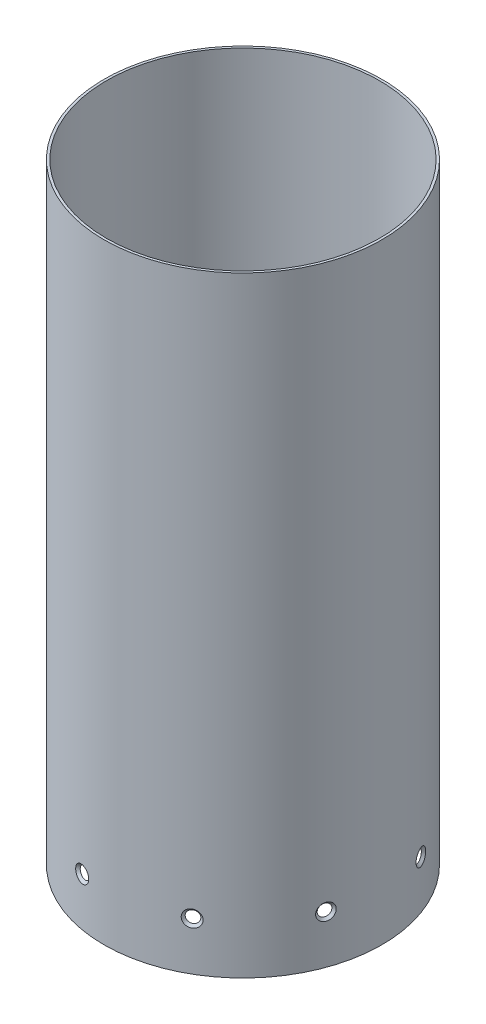
SolidWorks part; units mm, degrees
material "E-Glass Fiber"
ref_plane "Front Plane" through (0, 0, 0) normal (0, 0, 1) x (1, 0, 0)
ref_plane "Top Plane" through (0, 0, 0) normal (0, 1, 0) x (1, 0, 0)
ref_plane "Right Plane" through (0, 0, 0) normal (1, 0, 0) x (0, 0, -1)
sketch "Sketch1" plane through (0, 0, 0) normal (0, 1, 0) x (1, 0, 0)
  circle A0 centre (0, 0) radius 86.5
  circle A1 centre (0, 0) radius 85
extrude "Boss-Extrude1" add sketch "Sketch1" along normal blind 380
ref_plane "Plane2" through (0, 30, 0) normal (0, -1, 0) x (-1, 0, 0)
ref_plane "Plane1" through (-86.5, 0, 0) normal (-1, 0, 0) x (0, 0, 1)
sketch "Sketch2" plane through (-86.5, 0, 0) normal (-1, 0, 0) x (0, 0, 1)
  line L0 (-86.5, 0) -> (86.5, 0) construction
  circle A0 centre (0, 30) radius 2.75
  dimension "D1" = 30
extrude "Cut-Extrude1" cut sketch "Sketch2" against normal up to next
sketch "Sketch4" plane through (0, 30, 0) normal (0, -1, 0) x (1, 0, 0)
  line L1 (-93.9937, 0) -> (-74.5658, 0) construction
  line L6 (-86.3554, 0) -> (-86.3554, -5) construction
  line L7 (-86.3554, -5) -> (-81.3554, 0)
  line L8 (-86.3554, 0) -> (-81.3554, 0)
  line L9 (-86.3554, -5) -> (-87.969, -6.6136)
  line L10 (-87.969, -6.6136) -> (-87.969, 0)
  line L11 (-87.969, 0) -> (-86.3554, 0)
  circle A1 centre (0, 0) radius 86.5 construction
revolve "Cut-Revolve1" cut sketch "Sketch4" angle 360 about L1
pattern_circular "CirPattern1" count 9 over 360 about axis through (0, 0, 0) along (0, 1, 0) of "Cut-Revolve1"
